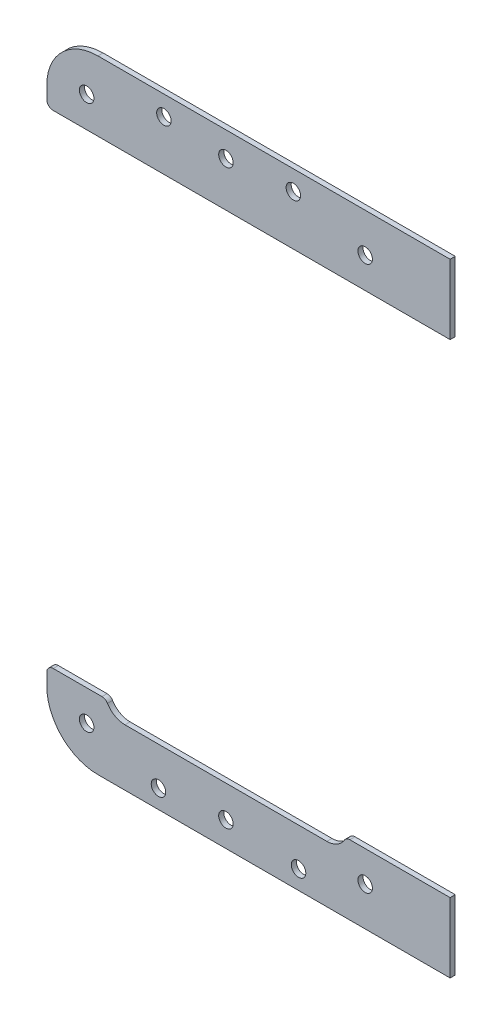
SolidWorks part; units mm, degrees
material "ASTM A36 Steel"
ref_plane "X-Y Datum" through (0, 0, 0) normal (0, 0, 1) x (1, 0, 0)
ref_plane "X-Z Datum" through (0, 0, 0) normal (0, 1, 0) x (1, 0, 0)
ref_plane "Y-Z Datum" through (0, 0, 0) normal (1, 0, 0) x (0, 0, -1)
sketch "Sketch2" plane through (0, 0, -401.5041) normal (0, 0, 1) x (1, 0, 0)
  line L1 (-6.6508, 25.9201) -> (-6.6508, 184.6701) construction
  line L3 (26.1152, 25.9201) -> (-39.4168, 25.9201) construction
  line L4 (-39.4168, 184.6701) -> (26.1152, 184.6701) construction
  line L5 (33.1665, 105.2951) -> (-46.3411, 105.2951) construction
  line L6 (33.1665, 179.3361) -> (33.1665, 31.2541) construction
  line L7 (-46.3411, 179.3361) -> (-46.3411, 31.2541) construction
  line L9 (48.9117, 8.7751) -> (-62.2133, 8.7751)
  line L10 (48.9117, 8.7751) -> (48.9117, 201.8151)
  line L11 (48.9117, 201.8151) -> (-62.2133, 201.8151)
  line L12 (-62.2133, 8.7751) -> (-62.2133, 201.8151)
  line L13 (48.9117, 8.7751) -> (-62.2133, 201.8151) construction
  line L14 (48.9117, 201.8151) -> (-62.2133, 8.7751) construction
  line L30 (29.671, 190.6701) -> (-1.1508, 190.6701)
  line L31 (-1.1508, 190.6701) -> (-1.1508, 194.0798)
  line L32 (-12.1508, 194.0798) -> (-12.1508, 190.6701)
  line L33 (-12.1508, 190.6701) -> (-42.9727, 190.6701)
  line L34 (-42.9727, 190.6701) -> (-45.9531, 193.6505)
  line L35 (-53.7313, 185.8723) -> (-50.7508, 182.8919)
  line L36 (-50.7508, 182.8919) -> (-50.7508, 138.9891)
  line L37 (-50.7508, 138.9891) -> (-54.1605, 138.9891)
  line L38 (-54.1605, 127.9891) -> (-50.7508, 127.9891)
  line L39 (-50.7508, 127.9891) -> (-50.7508, 82.6011)
  line L40 (-50.7508, 82.6011) -> (-54.1605, 82.6011)
  line L41 (-54.1605, 71.6011) -> (-50.7508, 71.6011)
  line L42 (-50.7508, 71.6011) -> (-50.7508, 27.6982)
  line L43 (-50.7508, 27.6982) -> (-53.7313, 24.7178)
  line L44 (-45.9531, 16.9396) -> (-42.9727, 19.9201)
  line L45 (-42.9727, 19.9201) -> (-12.1508, 19.9201)
  line L46 (-12.1508, 19.9201) -> (-12.1508, 16.5104)
  line L47 (-1.1508, 16.5104) -> (-1.1508, 19.9201)
  line L48 (-1.1508, 19.9201) -> (29.671, 19.9201)
  line L49 (29.671, 19.9201) -> (32.6514, 16.9396)
  line L50 (40.4296, 24.7178) -> (37.4492, 27.6982)
  line L51 (37.4492, 27.6982) -> (37.4492, 71.6011)
  line L52 (37.4492, 71.6011) -> (40.8589, 71.6011)
  line L53 (40.8589, 82.6011) -> (37.4492, 82.6011)
  line L54 (37.4492, 82.6011) -> (37.4492, 127.9891)
  line L55 (37.4492, 127.9891) -> (40.8589, 127.9891)
  line L56 (40.8589, 138.9891) -> (37.4492, 138.9891)
  line L57 (37.4492, 138.9891) -> (37.4492, 182.8919)
  line L58 (37.4492, 182.8919) -> (40.4296, 185.8723)
  line L59 (32.6514, 193.6505) -> (29.671, 190.6701)
  line L60 (29.671, 190.6701) -> (-1.1508, 190.6701)
  line L61 (-1.1508, 190.6701) -> (-1.1508, 194.0798)
  line L62 (-12.1508, 194.0798) -> (-12.1508, 190.6701)
  line L63 (-12.1508, 190.6701) -> (-42.9727, 190.6701)
  line L64 (-42.9727, 190.6701) -> (-45.9531, 193.6505)
  line L65 (-53.7313, 185.8723) -> (-50.7508, 182.8919)
  line L66 (-50.7508, 182.8919) -> (-50.7508, 138.9891)
  line L67 (-50.7508, 138.9891) -> (-54.1605, 138.9891)
  line L68 (-54.1605, 127.9891) -> (-50.7508, 127.9891)
  line L69 (-50.7508, 127.9891) -> (-50.7508, 82.6011)
  line L70 (-50.7508, 82.6011) -> (-54.1605, 82.6011)
  line L71 (-54.1605, 71.6011) -> (-50.7508, 71.6011)
  line L72 (-50.7508, 71.6011) -> (-50.7508, 27.6982)
  line L73 (-50.7508, 27.6982) -> (-53.7313, 24.7178)
  line L74 (-45.9531, 16.9396) -> (-42.9727, 19.9201)
  line L75 (-42.9727, 19.9201) -> (-12.1508, 19.9201)
  line L76 (-12.1508, 19.9201) -> (-12.1508, 16.5104)
  line L77 (-1.1508, 16.5104) -> (-1.1508, 19.9201)
  line L78 (-1.1508, 19.9201) -> (29.671, 19.9201)
  line L79 (29.671, 19.9201) -> (32.6514, 16.9396)
  line L80 (40.4296, 24.7178) -> (37.4492, 27.6982)
  line L81 (37.4492, 27.6982) -> (37.4492, 71.6011)
  line L82 (37.4492, 71.6011) -> (40.8589, 71.6011)
  line L83 (40.8589, 82.6011) -> (37.4492, 82.6011)
  line L84 (37.4492, 82.6011) -> (37.4492, 127.9891)
  line L85 (37.4492, 127.9891) -> (40.8589, 127.9891)
  line L86 (40.8589, 138.9891) -> (37.4492, 138.9891)
  line L87 (37.4492, 138.9891) -> (37.4492, 182.8919)
  line L88 (37.4492, 182.8919) -> (40.4296, 185.8723)
  line L89 (32.6514, 193.6505) -> (29.671, 190.6701)
  arc A10 (-1.1508, 194.0798) -> (-12.1508, 194.0798) centre (-6.6508, 194.0798) ccw
  arc A11 (-45.9531, 193.6505) -> (-53.7313, 185.8723) centre (-49.8422, 189.7614) ccw
  arc A12 (-54.1605, 138.9891) -> (-54.1605, 127.9891) centre (-54.1605, 133.4891) ccw
  arc A13 (-54.1605, 82.6011) -> (-54.1605, 71.6011) centre (-54.1605, 77.1011) ccw
  arc A14 (-53.7313, 24.7178) -> (-45.9531, 16.9396) centre (-49.8422, 20.8287) ccw
  arc A15 (-12.1508, 16.5104) -> (-1.1508, 16.5104) centre (-6.6508, 16.5104) ccw
  arc A16 (32.6514, 16.9396) -> (40.4296, 24.7178) centre (36.5405, 20.8287) ccw
  arc A17 (40.8589, 71.6011) -> (40.8589, 82.6011) centre (40.8589, 77.1011) ccw
  arc A18 (40.8589, 127.9891) -> (40.8589, 138.9891) centre (40.8589, 133.4891) ccw
  arc A19 (40.4296, 185.8723) -> (32.6514, 193.6505) centre (36.5405, 189.7614) ccw
  arc A20 (-1.1508, 194.0798) -> (-12.1508, 194.0798) centre (-6.6508, 194.0798) ccw
  arc A21 (-45.9531, 193.6505) -> (-53.7313, 185.8723) centre (-49.8422, 189.7614) ccw
  arc A22 (-54.1605, 138.9891) -> (-54.1605, 127.9891) centre (-54.1605, 133.4891) ccw
  arc A23 (-54.1605, 82.6011) -> (-54.1605, 71.6011) centre (-54.1605, 77.1011) ccw
  arc A24 (-53.7313, 24.7178) -> (-45.9531, 16.9396) centre (-49.8422, 20.8287) ccw
  arc A25 (-12.1508, 16.5104) -> (-1.1508, 16.5104) centre (-6.6508, 16.5104) ccw
  arc A26 (32.6514, 16.9396) -> (40.4296, 24.7178) centre (36.5405, 20.8287) ccw
  arc A27 (40.8589, 71.6011) -> (40.8589, 82.6011) centre (40.8589, 77.1011) ccw
  arc A28 (40.8589, 127.9891) -> (40.8589, 138.9891) centre (40.8589, 133.4891) ccw
  arc A29 (40.4296, 185.8723) -> (32.6514, 193.6505) centre (36.5405, 189.7614) ccw
  point P41 (-6.6508, 105.2951)
  dimension "D2" = 111.125
  dimension "D3" = 193.04
  dimension "D1" = 0
extrude "Boss-Extrude1" add sketch "Sketch2" along normal blind 1.5875 contours L12 L9 L10 L11 A29 L88 L87 L86 A28 L85 L84 L83 A27 L82 L81 L80 A26 L79 L78 L77 A25 L76 L75 L74 A24 L73 L72 L71 A23 L70 L69 L68 A22 L67 L66 L65 A21 L64 L63 L62 A20 L61 L60 L89 | L88 A29 L89 L60 L61 A20 L62 L63 L64 A21 L65 L66 L67 A22 L68 L69 L70 A23 L71 L72 L73 A24 L74 L75 L76 A25 L77 L78 L79 A26 L80 L81 L82 A27 L83 L84 L85 A28 L86 L87 region at (-6.6508, 11.0025, -401.5041) region at (-6.6508, 105.2951, -401.5041)
hole_wizard "M4 Clearance Hole1" positions "Sketch3" profile "Sketch4" hole size "M4" standard "ANSI Metric" end condition through all
sketch "Sketch3" plane through (0, 0, -399.9166) normal (0, 0, 1) x (1, 0, 0)
  point P0 (36.5405, 189.7614)
  point P3 (-6.6508, 194.0798)
  point P6 (-49.8422, 189.7614)
  point P9 (-54.1605, 133.4891)
  point P12 (-54.1605, 77.1011)
  point P15 (-49.8422, 20.8287)
  point P18 (-6.6508, 16.5104)
  point P21 (36.5405, 20.8287)
  point P24 (40.8589, 77.1011)
  point P27 (40.8589, 133.4891)
  point P42 (14.2601, 195.6701)
  point P44 (-55.7508, 105.2951)
  point P46 (-27.5617, 14.9201)
sketch "Sketch4" plane through (36.5405, 189.7614, -399.9166) normal (1, 0, 0) x (0, -1, 0)
  line L0 (0, 0) -> (0, 1.5875)
  line L1 (0, 1.5875) -> (2.25, 1.5875)
  line L2 (2.25, 1.5875) -> (2.25, 0)
  line L5 (2.25, 0) -> (0, 0)
  line L11 (0, -6.35) -> (0, 107.95) construction
  dimension "Thru Hole Dia." = 4.5
  dimension "Thru Hole Depth" = 1.5875
fillet "Fillet1" radius 15.875 2 edges at (-62.2133, 201.8151, -400.7104) (-62.2133, 8.7751, -400.7104)
sketch "Sketch6" plane through (0, 0, -399.9166) normal (0, 0, 1) x (1, 0, 0)
  line L0 (21.2892, 43.3826) -> (-34.5908, 43.3826) construction
  line L3 (-6.6508, 25.9201) -> (-6.6508, 184.6701) construction
  line L4 (-62.2133, 8.7751) -> (48.9117, 8.7751)
  line L5 (48.9117, 8.7751) -> (48.9117, 201.8151)
  line L6 (48.9117, 201.8151) -> (-62.2133, 201.8151)
  line L7 (-62.2133, 201.8151) -> (-62.2133, 8.7751)
  line L8 (-62.2133, 8.7751) -> (48.9117, 8.7751) construction
  line L9 (48.9117, 8.7751) -> (48.9117, 201.8151) construction
  line L10 (48.9117, 201.8151) -> (-62.2133, 201.8151) construction
  line L11 (-62.2133, 201.8151) -> (-62.2133, 8.7751) construction
  line L14 (-6.6508, 25.9201) -> (-6.6508, 60.8451) construction
  line L18 (31.4492, 63.3451) -> (31.4492, 179.3361)
  line L19 (26.1152, 184.6701) -> (-39.4168, 184.6701)
  line L24 (-44.7508, 179.3361) -> (-44.7508, 63.3451)
  line L25 (-44.7508, 63.3451) -> (31.4492, 63.3451)
  line L26 (31.4492, 63.3451) -> (31.4492, 179.3361)
  line L27 (26.1152, 184.6701) -> (-39.4168, 184.6701)
  line L28 (-44.7508, 179.3361) -> (-44.7508, 63.3451)
  line L29 (-44.7508, 63.3451) -> (31.4492, 63.3451)
  line L30 (33.0395, 31.2541) -> (33.0395, 179.3361)
  line L31 (-39.4168, 24.3298) -> (26.1152, 24.3298)
  line L32 (-46.3411, 179.3361) -> (-46.3411, 31.2541)
  line L33 (26.1152, 186.2604) -> (-39.4168, 186.2604)
  line L34 (33.0395, 31.2541) -> (33.0395, 179.3361)
  line L35 (-39.4168, 24.3298) -> (26.1152, 24.3298)
  line L36 (-46.3411, 179.3361) -> (-46.3411, 31.2541)
  line L37 (26.1152, 186.2604) -> (-39.4168, 186.2604)
  line L38 (37.4492, 138.9891) -> (37.4492, 182.8919)
  line L39 (37.4492, 182.8919) -> (40.4296, 185.8723)
  line L40 (32.6514, 193.6505) -> (29.671, 190.6701)
  line L41 (29.671, 190.6701) -> (-1.1508, 190.6701)
  line L42 (-1.1508, 190.6701) -> (-1.1508, 194.0798)
  line L43 (-12.1508, 194.0798) -> (-12.1508, 190.6701)
  line L44 (-12.1508, 190.6701) -> (-42.9727, 190.6701)
  line L45 (-42.9727, 190.6701) -> (-45.9531, 193.6505)
  line L46 (-53.7313, 185.8723) -> (-50.7508, 182.8919)
  line L47 (-50.7508, 182.8919) -> (-50.7508, 138.9891)
  line L48 (-50.7508, 138.9891) -> (-54.1605, 138.9891)
  line L49 (-54.1605, 127.9891) -> (-50.7508, 127.9891)
  line L50 (-50.7508, 127.9891) -> (-50.7508, 82.6011)
  line L51 (-50.7508, 82.6011) -> (-54.1605, 82.6011)
  line L52 (-54.1605, 71.6011) -> (-50.7508, 71.6011)
  line L53 (-50.7508, 71.6011) -> (-50.7508, 27.6982)
  line L54 (-50.7508, 27.6982) -> (-53.7313, 24.7178)
  line L55 (-45.9531, 16.9396) -> (-42.9727, 19.9201)
  line L56 (-42.9727, 19.9201) -> (-12.1508, 19.9201)
  line L57 (-12.1508, 19.9201) -> (-12.1508, 16.5104)
  line L58 (-1.1508, 16.5104) -> (-1.1508, 19.9201)
  line L59 (-1.1508, 19.9201) -> (29.671, 19.9201)
  line L60 (29.671, 19.9201) -> (32.6514, 16.9396)
  line L61 (40.4296, 24.7178) -> (37.4492, 27.6982)
  line L62 (37.4492, 27.6982) -> (37.4492, 71.6011)
  line L63 (37.4492, 71.6011) -> (40.8589, 71.6011)
  line L64 (40.8589, 82.6011) -> (37.4492, 82.6011)
  line L65 (37.4492, 82.6011) -> (37.4492, 127.9891)
  line L66 (37.4492, 127.9891) -> (40.8589, 127.9891)
  line L67 (40.8589, 138.9891) -> (37.4492, 138.9891)
  line L68 (37.4492, 138.9891) -> (37.4492, 182.8919) construction
  line L69 (37.4492, 182.8919) -> (40.4296, 185.8723) construction
  line L70 (32.6514, 193.6505) -> (29.671, 190.6701) construction
  line L71 (29.671, 190.6701) -> (-1.1508, 190.6701) construction
  line L72 (-1.1508, 190.6701) -> (-1.1508, 194.0798) construction
  line L73 (-12.1508, 194.0798) -> (-12.1508, 190.6701) construction
  line L74 (-12.1508, 190.6701) -> (-42.9727, 190.6701) construction
  line L75 (-42.9727, 190.6701) -> (-45.9531, 193.6505) construction
  line L76 (-53.7313, 185.8723) -> (-50.7508, 182.8919) construction
  line L77 (-50.7508, 182.8919) -> (-50.7508, 138.9891) construction
  line L78 (-50.7508, 138.9891) -> (-54.1605, 138.9891) construction
  line L79 (-54.1605, 127.9891) -> (-50.7508, 127.9891) construction
  line L80 (-50.7508, 127.9891) -> (-50.7508, 82.6011) construction
  line L81 (-50.7508, 82.6011) -> (-54.1605, 82.6011) construction
  line L82 (-54.1605, 71.6011) -> (-50.7508, 71.6011) construction
  line L83 (-50.7508, 71.6011) -> (-50.7508, 27.6982) construction
  line L84 (-50.7508, 27.6982) -> (-53.7313, 24.7178) construction
  line L85 (-45.9531, 16.9396) -> (-42.9727, 19.9201) construction
  line L86 (-42.9727, 19.9201) -> (-12.1508, 19.9201) construction
  line L87 (-12.1508, 19.9201) -> (-12.1508, 16.5104) construction
  line L88 (-1.1508, 16.5104) -> (-1.1508, 19.9201) construction
  line L89 (-1.1508, 19.9201) -> (29.671, 19.9201) construction
  line L90 (29.671, 19.9201) -> (32.6514, 16.9396) construction
  line L91 (40.4296, 24.7178) -> (37.4492, 27.6982) construction
  line L92 (37.4492, 27.6982) -> (37.4492, 71.6011) construction
  line L93 (37.4492, 71.6011) -> (40.8589, 71.6011) construction
  line L94 (40.8589, 82.6011) -> (37.4492, 82.6011) construction
  line L95 (37.4492, 82.6011) -> (37.4492, 127.9891) construction
  line L96 (37.4492, 127.9891) -> (40.8589, 127.9891) construction
  line L97 (40.8589, 138.9891) -> (37.4492, 138.9891) construction
  line L98 (31.4492, 31.2541) -> (31.4492, 60.8451)
  line L99 (31.4492, 60.8451) -> (-44.7508, 60.8451)
  line L100 (-44.7508, 60.8451) -> (-44.7508, 31.2541)
  line L101 (-39.4168, 25.9201) -> (26.1152, 25.9201)
  line L102 (31.4492, 31.2541) -> (31.4492, 60.8451)
  line L103 (31.4492, 60.8451) -> (-44.7508, 60.8451)
  line L104 (-44.7508, 60.8451) -> (-44.7508, 31.2541)
  line L105 (-39.4168, 25.9201) -> (26.1152, 25.9201)
  line L152 (3.5092, 43.3826) -> (-16.8108, 43.3826) construction
  circle A0 centre (-34.5908, 43.3826) radius 2.4003
  circle A1 centre (21.2892, 43.3826) radius 2.4003
  circle A2 centre (-20.8847, 82.7899) radius 3
  circle A3 centre (7.5831, 106.4243) radius 3
  arc A4 (31.4492, 179.3361) -> (26.1152, 184.6701) centre (26.1152, 179.3361) ccw
  arc A5 (-39.4168, 184.6701) -> (-44.7508, 179.3361) centre (-39.4168, 179.3361) ccw
  arc A6 (31.4492, 179.3361) -> (26.1152, 184.6701) centre (26.1152, 179.3361) ccw
  arc A7 (-39.4168, 184.6701) -> (-44.7508, 179.3361) centre (-39.4168, 179.3361) ccw
  arc A8 (-44.7508, 31.2541) -> (-39.4168, 25.9201) centre (-39.4168, 31.2541) ccw
  arc A9 (26.1152, 25.9201) -> (31.4492, 31.2541) centre (26.1152, 31.2541) ccw
  arc A10 (40.4296, 185.8723) -> (32.6514, 193.6505) centre (36.5405, 189.7614) ccw
  arc A11 (-1.1508, 194.0798) -> (-12.1508, 194.0798) centre (-6.6508, 194.0798) ccw
  arc A12 (-45.9531, 193.6505) -> (-53.7313, 185.8723) centre (-49.8422, 189.7614) ccw
  arc A13 (-54.1605, 138.9891) -> (-54.1605, 127.9891) centre (-54.1605, 133.4891) ccw
  arc A14 (-54.1605, 82.6011) -> (-54.1605, 71.6011) centre (-54.1605, 77.1011) ccw
  arc A15 (-53.7313, 24.7178) -> (-45.9531, 16.9396) centre (-49.8422, 20.8287) ccw
  arc A16 (-12.1508, 16.5104) -> (-1.1508, 16.5104) centre (-6.6508, 16.5104) ccw
  arc A17 (32.6514, 16.9396) -> (40.4296, 24.7178) centre (36.5405, 20.8287) ccw
  arc A18 (40.8589, 71.6011) -> (40.8589, 82.6011) centre (40.8589, 77.1011) ccw
  arc A19 (40.8589, 127.9891) -> (40.8589, 138.9891) centre (40.8589, 133.4891) ccw
  arc A20 (40.4296, 185.8723) -> (32.6514, 193.6505) centre (36.5405, 189.7614) ccw construction
  arc A21 (-1.1508, 194.0798) -> (-12.1508, 194.0798) centre (-6.6508, 194.0798) ccw construction
  arc A22 (-45.9531, 193.6505) -> (-53.7313, 185.8723) centre (-49.8422, 189.7614) ccw construction
  arc A23 (-54.1605, 138.9891) -> (-54.1605, 127.9891) centre (-54.1605, 133.4891) ccw construction
  arc A24 (-54.1605, 82.6011) -> (-54.1605, 71.6011) centre (-54.1605, 77.1011) ccw construction
  arc A25 (-53.7313, 24.7178) -> (-45.9531, 16.9396) centre (-49.8422, 20.8287) ccw construction
  arc A26 (-12.1508, 16.5104) -> (-1.1508, 16.5104) centre (-6.6508, 16.5104) ccw construction
  arc A27 (32.6514, 16.9396) -> (40.4296, 24.7178) centre (36.5405, 20.8287) ccw construction
  arc A28 (40.8589, 71.6011) -> (40.8589, 82.6011) centre (40.8589, 77.1011) ccw construction
  arc A29 (40.8589, 127.9891) -> (40.8589, 138.9891) centre (40.8589, 133.4891) ccw construction
  arc A30 (26.1152, 24.3298) -> (33.0395, 31.2541) centre (26.1152, 31.2541) ccw
  arc A31 (-46.3411, 31.2541) -> (-39.4168, 24.3298) centre (-39.4168, 31.2541) ccw
  arc A32 (-39.4168, 186.2604) -> (-46.3411, 179.3361) centre (-39.4168, 179.3361) ccw
  arc A33 (33.0395, 179.3361) -> (26.1152, 186.2604) centre (26.1152, 179.3361) ccw
  arc A34 (26.1152, 24.3298) -> (33.0395, 31.2541) centre (26.1152, 31.2541) ccw
  arc A35 (-46.3411, 31.2541) -> (-39.4168, 24.3298) centre (-39.4168, 31.2541) ccw
  arc A36 (-39.4168, 186.2604) -> (-46.3411, 179.3361) centre (-39.4168, 179.3361) ccw
  arc A37 (33.0395, 179.3361) -> (26.1152, 186.2604) centre (26.1152, 179.3361) ccw
  arc A38 (-44.7508, 31.2541) -> (-39.4168, 25.9201) centre (-39.4168, 31.2541) ccw
  arc A39 (26.1152, 25.9201) -> (31.4492, 31.2541) centre (26.1152, 31.2541) ccw
  circle A40 centre (-20.8847, 142.5908) radius 3
  circle A41 centre (7.5831, 166.2252) radius 3
  circle A44 centre (-20.8847, 142.5908) radius 4.675
  circle A46 centre (7.5831, 166.2252) radius 4.675
  circle A48 centre (-20.8847, 82.7899) radius 4.675
  circle A50 centre (7.5831, 106.4243) radius 4.675
  circle A71 centre (3.5092, 43.3826) radius 6.477
  circle A72 centre (-16.8108, 43.3826) radius 6.477
  circle A169 centre (-33.3208, 123.6701) radius 6.477
  circle A573 centre (-6.6508, 94.6071) radius 10 construction
  circle A574 centre (-6.6508, 154.408) radius 10 construction
  circle A607 centre (-6.6508, 154.408) radius 10.762
  circle A608 centre (-6.6508, 94.6071) radius 10.762
  point P29 (-6.6508, 43.3826)
  point P90 (-6.6508, 43.3826)
  point P96 (-6.6508, 43.3826)
  point P99 (7.5831, 166.2252)
  point P100 (-20.8847, 142.5908)
  point P101 (7.5831, 106.4243)
  point P102 (-20.8847, 82.7899)
  dimension "D7" = 4.8006
  dimension "D9" = 12.954
  dimension "D11" = 20
  dimension "D13" = 6
  dimension "D3" = 55.88
  dimension "D8" = 20.32
  dimension "D10" = 11.43
  dimension "2" = 60.325
  dimension "D12" = 0.762
  dimension "D1" = 0
  dimension "D2" = 0
  dimension "D4" = 0
  dimension "D5" = 0
  dimension "D6" = 0
extrude "Cut-Extrude1" cut sketch "Sketch6" against normal through all contours A71 | A1 | A72 | A0 | A169 | A40 | A41 | A608 | A607 region at (-34.5908, 43.3826, -399.9166) region at (21.2892, 43.3826, -399.9166) region at (-20.8847, 142.5908, -399.9166) region at (7.5831, 166.2252, -399.9166) region at (3.5092, 43.3826, -399.9166) region at (-16.8108, 43.3826, -399.9166) region at (-33.3208, 123.6701, -399.9166) region at (-6.6508, 154.408, -399.9166) region at (-6.6508, 94.6071, -399.9166)
sketch "Sketch7" plane through (0, 0, -399.9166) normal (0, 0, 1) x (1, 0, 0)
  line L0 (48.9117, 201.8151) -> (-46.3383, 201.8151) construction
  line L1 (48.9117, 201.8151) -> (62.8817, 201.8151)
  line L2 (48.9117, 201.8151) -> (48.9117, 8.7751)
  line L3 (48.9117, 8.7751) -> (62.8817, 8.7751)
  line L4 (62.8817, 201.8151) -> (62.8817, 8.7751)
  line L5 (48.9117, 8.7751) -> (-46.3383, 8.7751) construction
  dimension "D1" = 13.97
extrude "Boss-Extrude2" add sketch "Sketch7" against normal blind 1.5875
sketch "Sketch8" plane through (0, 0, -399.9166) normal (0, 0, 1) x (1, 0, 0)
  line L0 (31.0114, 173.458) -> (-44.3131, 173.458)
  line L1 (31.0114, 26.3578) -> (-44.3131, 26.3578)
  line L2 (31.0114, 26.3578) -> (31.0114, 184.2323)
  line L3 (31.0114, 184.2323) -> (-44.3131, 184.2323)
  line L4 (-44.3131, 26.3578) -> (-44.3131, 184.2323)
  line L5 (31.0114, 26.3578) -> (-44.3131, 184.2323) construction
  line L6 (31.0114, 184.2323) -> (-44.3131, 26.3578) construction
  line L7 (31.0114, 135.358) -> (-44.3131, 135.358)
  line L8 (31.0114, 78.7321) -> (-44.3131, 78.7321)
  line L10 (31.0114, 123.6701) -> (-44.3131, 123.6701) construction
  line L11 (-44.3131, 60.8451) -> (31.0114, 60.8451)
  line L12 (31.0114, 110.4821) -> (-44.3131, 110.4821)
  line L13 (31.0114, 154.408) -> (-44.3131, 154.408)
  line L14 (31.0114, 94.6071) -> (-44.3131, 94.6071)
  circle A0 centre (-33.3208, 123.6701) radius 8.9535
  circle A1 centre (-33.3208, 123.6701) radius 7.366 construction
  point P0 (-6.6508, 105.2951)
  point P22 (-133.0715, 19.9201)
  point P23 (-133.0715, 19.9201)
  point P27 (-133.0715, 19.9201)
  circle M1 centre (7.5831, 166.2252) radius 3
  circle M3 centre (-20.8847, 142.5908) radius 3
  circle M5 centre (-33.3208, 123.6701) radius 6.477
  circle M6 centre (-34.5908, 43.3826) radius 2.4003
  circle M7 centre (-16.8108, 43.3826) radius 6.477
  circle M8 centre (21.2892, 43.3826) radius 2.4003
  circle M9 centre (-6.6508, 94.6071) radius 10.762
  circle M10 centre (-6.6508, 154.408) radius 10.762
  circle M11 centre (3.5092, 43.3826) radius 6.477
  dimension "D2" = 19.05
  dimension "D3" = 19.05
  dimension "D4" = 15.875
  dimension "D1" = 1.5875
  dimension "D5" = 15.875
extrude "Cut-Extrude2" cut sketch "Sketch8" against normal blind 1.5875 contours L2 L4 L1 M6 M8 M11 M7 | L2 L4 M3 M9 | L2 L3 L4 M10 M1 | A0 M5 | L14 L2 L12 L4 M9 M3 | L2 L13 L4 L7 M10 M1 region at (30.2344, 163.933, -399.9166) region at (30.2344, 144.883, -399.9166) region at (30.2416, 102.5446, -399.9166) region at (30.2416, 86.6696, -399.9166) region at (-6.6508, 43.63, -399.9166) region at (-42.0211, 123.6701, -399.9166)
fillet "Fillet2" radius 9.525 4 edges at (-44.3131, 173.458, -400.7104) (-44.3131, 135.358, -400.7104) (31.0114, 135.358, -400.7104) (31.0114, 173.458, -400.7104)
fillet "Fillet3" radius 6.35 4 edges at (-44.3131, 26.3578, -400.7104) (31.0114, 26.3578, -400.7104) (31.0114, 60.8451, -400.7104) (-44.3131, 60.8451, -400.7104)
fillet "Fillet4" radius 9.525 4 edges at (-44.3131, 110.4821, -400.7104) (-44.3131, 78.7321, -400.7104) (31.0114, 78.7321, -400.7104) (31.0114, 110.4821, -400.7104)
sketch "Sketch9" plane through (0, 0, -399.9166) normal (0, 0, 1) x (1, 0, 0)
  line L1 (-62.2133, 24.6501) -> (-62.2133, 185.9401) construction
  line L3 (62.8817, 8.7751) -> (62.8817, 201.8151) construction
  line L4 (62.8817, 180.2251) -> (62.8817, 30.3651)
  line L6 (-62.2133, 180.2251) -> (-62.2133, 30.3651)
  line L11 (-62.2133, 180.2251) -> (62.8817, 180.2251)
  line L16 (-62.2133, 30.3651) -> (62.8817, 30.3651)
extrude "Cut-Extrude5" cut sketch "Sketch9" against normal blind 80
fillet "Fillet6" radius 2 1 edges at (-62.2133, 30.3651, -400.7104)
fillet "Fillet8" radius 2 1 edges at (-43.8651, 30.3651, -400.7104)
fillet "Fillet9" radius 2 1 edges at (30.5634, 30.3651, -400.7104)
fillet "Fillet10" radius 2 1 edges at (-62.2133, 180.2251, -400.7104)
sketch "Sketch17" plane through (0, 0, -401.5041) normal (0, 0, -1) x (-1, 0, 0)
  circle A0 centre (-15.869, 14.5547) radius 2.25
extrude "Cut-Extrude12" cut sketch "Sketch17" against normal blind 72.5925 contours A0
sketch "Sketch18" plane through (0, 0, -401.5041) normal (0, 0, -1) x (-1, 0, 0)
  circle A0 centre (27.5617, 14.9201) radius 2.25
extrude "Boss-Extrude9" add sketch "Sketch18" against normal blind 1.5875
sketch "Sketch20" plane through (0, 0, -401.5041) normal (0, 0, -1) x (-1, 0, 0)
  circle A0 centre (27.565, 14.5547) radius 2.25
  circle A1 centre (25.8719, 195.6701) radius 2.25
extrude "Cut-Extrude18" cut sketch "Sketch20" against normal blind 17.5875
